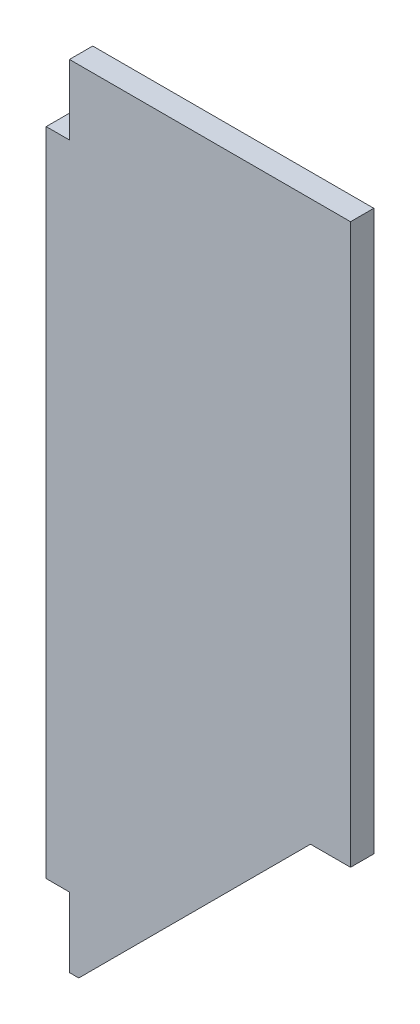
SolidWorks part; units mm, degrees
ref_plane "Front" through (0, 0, 0) normal (0, 0, 1) x (1, 0, 0)
ref_plane "Top" through (0, 0, 0) normal (0, 1, 0) x (1, 0, 0)
ref_plane "Right" through (0, 0, 0) normal (1, 0, 0) x (0, 0, -1)
sketch "Sketch1" plane through (0, 0, 0) normal (0, 0, 1) x (1, 0, 0)
  line L0 (0, -215.9) -> (8.89, -215.9)
  line L2 (0, 0) -> (0, -215.9)
  line L5 (8.89, -215.9) -> (72.1487, -152.6413)
  line L8 (76.7305, 0) -> (0, 0)
  line L9 (76.7305, 60.287) -> (76.7305, -158.2265) construction
  line L11 (72.1487, -152.6413) -> (83.0805, -152.6413)
  line L12 (76.7305, 0) -> (83.0805, 0)
  line L13 (83.0805, 0) -> (83.0805, -152.6413)
  line L14 (83.0805, 9.487) -> (83.0805, -160.8568) construction
  point P1 (0, 0)
  dimension "D1" = 215.9
  dimension "D2" = 8.89
  dimension "D3" = 135
extrude "Boss-Extrude1" add sketch "Sketch1" along normal blind 6.35
sketch "Sketch2" plane through (0, 0, 6.35) normal (0, 0, 1) x (1, 0, 0)
  line L1 (0, 0) -> (6.35, 0)
  line L2 (0, 0) -> (0, -19.05)
  line L3 (0, -19.05) -> (6.35, -19.05)
  line L4 (6.35, 0) -> (6.35, -19.05)
  line L5 (0, -215.9) -> (6.35, -215.9)
  line L6 (0, -215.9) -> (0, -196.85)
  line L7 (0, -196.85) -> (6.35, -196.85)
  line L8 (6.35, -215.9) -> (6.35, -196.85)
  dimension "D1" = 6.35
  dimension "D2" = 19.05
  dimension "D3" = 6.35
  dimension "D4" = 19.05
extrude "Cut-Extrude1" cut sketch "Sketch2" against normal through all
